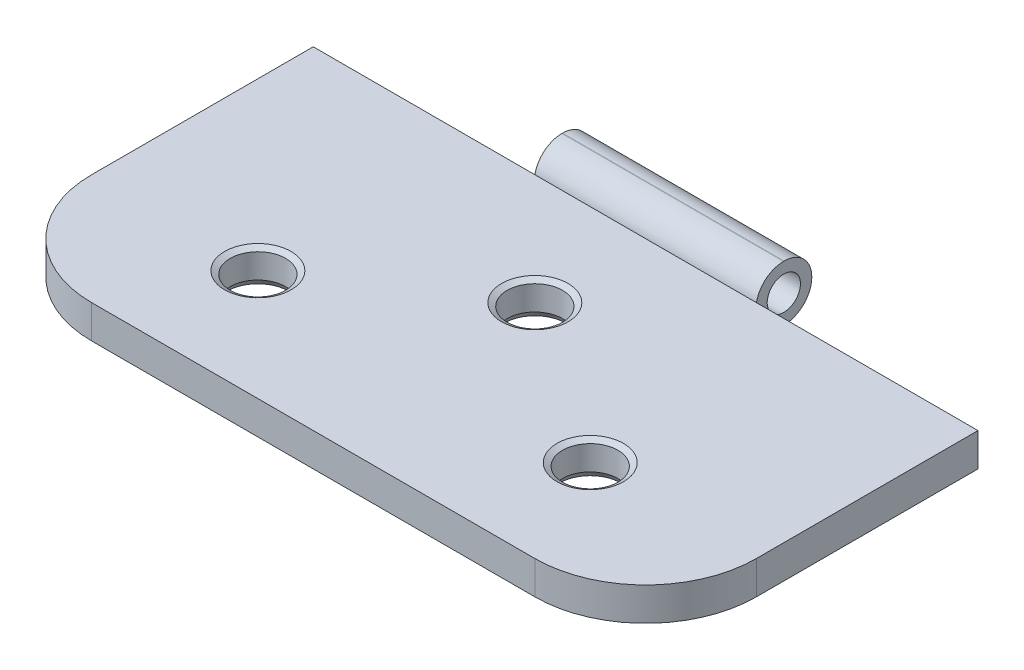
SolidWorks part; units mm, degrees
ref_plane "Front Plane" through (0, 0, 0) normal (0, 0, 1) x (1, 0, 0)
ref_plane "Top Plane" through (0, 0, 0) normal (0, 1, 0) x (1, 0, 0)
ref_plane "Right Plane" through (0, 0, 0) normal (1, 0, 0) x (0, 0, -1)
sketch "Szkic1" plane through (0, 0, 0) normal (0, 1, 0) x (1, 0, 0)
  line L1 (-30, 15) -> (30, 15)
  line L2 (-30, 15) -> (-30, -15)
  line L3 (-30, -15) -> (30, -15)
  line L4 (30, 15) -> (30, -15)
  line L5 (-30, 15) -> (30, -15) construction
  line L6 (-30, -15) -> (30, 15) construction
  point P0 (0, 0)
  dimension "D1" = 60
  dimension "D2" = 30
extrude "Dodanie-wyciągnięcie1" add sketch "Szkic1" along normal blind 3
sketch "Szkic2" plane through (0, 3, 0) normal (0, 1, 0) x (1, 0, 0)
  line L0 (0, 15) -> (0, 5) construction
  line L1 (30, 15) -> (-30, 15) construction
  line L2 (0, -15) -> (0, -5) construction
  line L3 (-30, -15) -> (30, -15) construction
  line L4 (0, -5) -> (30, -5) construction
  line L5 (30, -15) -> (30, 15) construction
  line L6 (0, -5) -> (-30, -5) construction
  line L7 (-30, 15) -> (-30, -15) construction
  circle A0 centre (-15, -5) radius 2.5
  circle A1 centre (15, -5) radius 2.5
  circle A2 centre (0, 5) radius 2.5
  dimension "D1" = 5
  dimension "D2" = 5
  dimension "D3" = 5
extrude "Wytnij-wyciągnięcie1" cut sketch "Szkic2" against normal blind 5
fillet "Zaokrąglenie1" radius 10 2 edges at (-30, 1.5, 15) (30, 1.5, 15)
sketch "Szkic3" plane through (0, 0, -15) normal (0, 0, -1) x (-1, 0, 0)
  line L0 (-30, 0) -> (-10, 0) construction
  line L1 (-30, 0) -> (30, 0) construction
  line L2 (-30, 3) -> (30, 3) construction
  line L3 (-10, 0) -> (10, 0)
  line L4 (-10, 0) -> (-10, 3)
  line L5 (-10, 3) -> (10, 3)
  line L6 (10, 0) -> (10, 3)
  dimension "D1" = 20
extrude "Dodanie-wyciągnięcie2" add sketch "Szkic3" along normal blind 5
sketch "Szkic4" plane through (0, 3, 0) normal (0, 1, 0) x (1, 0, 0)
  line L1 (10, 20) -> (-10, 20)
  line L2 (10, 20) -> (10, 15)
  line L3 (10, 15) -> (-10, 15)
  line L4 (-10, 20) -> (-10, 15)
extrude "Dodanie-wyciągnięcie3" add sketch "Szkic4" along normal blind 2
fillet "Zaokrąglenie2" radius 2.5 3 edges at (0, 0, -20) (0, 5, -20) (0, 5, -15)
sketch "Szkic5" plane through (10, 0, 0) normal (1, 0, 0) x (0, 0, -1)
  line L0 (17.4495, 5) -> (17.5, 0) construction
  circle A0 centre (17.4747, 2.5) radius 1.5
extrude "Wytnij-wyciągnięcie2" cut sketch "Szkic5" against normal blind 20
chamfer "Sfazowanie1" distance 0.5 angle 30 1 edges at (0, 3, -2.5) first distance on face at (0, 3, -1.9822)
chamfer "Sfazowanie2" distance 0.5 angle 30 5 edges at (15, 0, 7.5) (0, 0, -2.5) (-15, 0, 7.5) (15, 3, 7.5) (-15, 3, 7.5) first distance on face at (15, 3, 7.5) first distance on face at (0, 2.7113, -2.5) first distance on face at (-15, 3, 7.5) first distance on face at (0, 3, -2)
